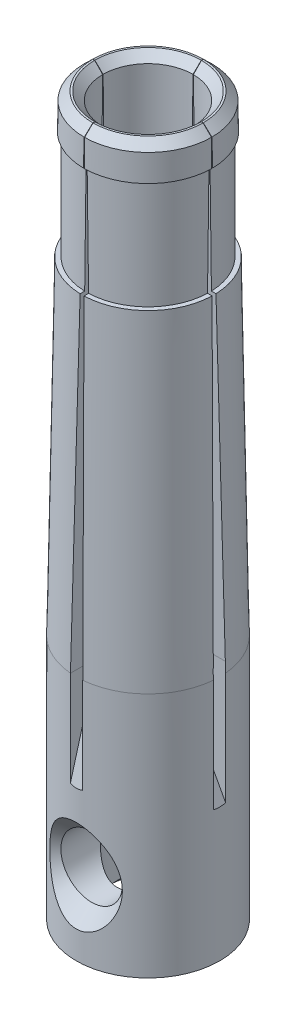
SolidWorks part; units mm, degrees
material "Brass"
ref_plane "Front Plane" through (0, 0, 0) normal (0, 0, 1) x (1, 0, 0)
ref_plane "Top Plane" through (0, 0, 0) normal (0, 1, 0) x (1, 0, 0)
ref_plane "Right Plane" through (0, 0, 0) normal (1, 0, 0) x (0, 0, -1)
sketch "Sketch1" plane through (0, 0, 0) normal (0, 0, 1) x (1, 0, 0)
  line L1 (0, 0) -> (3.5, 0)
  line L2 (0, 0) -> (0, 12)
  line L3 (0, 12) -> (3.5, 12)
  line L4 (3.5, 0) -> (3.5, 12)
  line L5 (0, 12) -> (3.5, 12)
  line L6 (0, 12) -> (0, 35)
  line L7 (0, 35) -> (3.1, 35)
  line L8 (3.5, 12) -> (3.1, 35)
  dimension "D1" = 3.5
  dimension "D2" = 12
  dimension "D3" = 3.1
  dimension "D4" = 35
revolve "Revolve1" add sketch "Sketch1" angle 360 about L2 region at (1.75, 6, 0) region at (1.652, 23.2677, 0)
sketch "Sketch2" plane through (0, 35, 0) normal (0, 1, 0) x (1, 0, 0)
  circle A0 centre (0, 0) radius 2.2
  dimension "D1" = 4.4
extrude "Cut-Extrude1" cut sketch "Sketch2" against normal blind 23
sketch "Sketch3" plane through (0, 0, 0) normal (0, -1, 0) x (1, 0, 0)
  line L0 (0, 0) -> (0, 50000) construction
  circle A0 centre (0, -0.5026) radius 2
  dimension "D1" = 4
extrude "Cut-Extrude2" cut sketch "Sketch3" against normal blind 9
ref_plane "Plane1" through (-3.5, 0, 0) normal (-1, 0, 0) x (0, 0, 1)
ref_plane "Plane2" through (0, 0, 3.5) normal (0, 0, 1) x (1, 0, 0)
sketch "Sketch5" plane through (-3.5, 0, 0) normal (-1, 0, 0) x (0, 0, 1)
  line L0 (0, 0) -> (0, 50000) construction
  line L1 (3.5, 12) -> (-3.5, 12) construction
  line L2 (3.5, 12) -> (-3.5, 12) construction
  line L3 (2.2, 35) -> (-2.2, 35) construction
  line L4 (3.1, 35) -> (-3.1, 35) construction
  line L5 (-3.5, 0) -> (3.5, 0) construction
  line L6 (0.3, 12) -> (-0.3, 12)
  line L7 (0.3, 12) -> (0.005, 35)
  line L8 (0.005, 35) -> (-0.005, 35)
  line L9 (-0.3, 12) -> (-0.005, 35)
  point P7 (0, 12)
  point P12 (0, 35)
  dimension "D1" = 12
  dimension "D2" = 0.6
  dimension "D3" = 0.01
extrude "Cut-Extrude3" cut sketch "Sketch5" against normal through all
sketch "Sketch9" plane through (0, 0, 3.5) normal (0, 0, 1) x (1, 0, 0)
  line L0 (3.1, 35) -> (-3.1, 35) construction
  line L1 (-3.5, 0) -> (3.5, 0) construction
  line L2 (-3.5, 9.5) -> (3.51, 9.5) construction
  line L3 (3.1, 35) -> (-3.1, 35) construction
  line L4 (0.005, 9.5) -> (0.005, 50009.5) construction
  line L8 (0.305, 12) -> (-0.295, 12)
  line L9 (0.305, 12) -> (0.01, 35)
  line L10 (0.01, 35) -> (0, 35)
  line L11 (-0.295, 12) -> (0, 35)
  point P6 (0.005, 9.5)
  point P7 (0.005, 35)
  point P13 (0.005, 12)
  dimension "D3" = 0.6
  dimension "D4" = 0.01
  dimension "D1" = 12
extrude "Cut-Extrude4" cut sketch "Sketch9" against normal through all
sketch "Sketch11" plane through (0, 0, 0) normal (0, 0, 1) x (1, 0, 0)
  line L0 (-3.5007, 0) -> (-3.5007, 11.8403) construction
  line L1 (-3.5007, 11.8403) -> (-3.4891, 11.8403) construction
  line L2 (-3.4891, 11.8403) -> (-3.1061, 34.8404) construction
  line L3 (-3.1061, 34.8404) -> (-0.0061, 31.7412) construction
  line L4 (-0.0061, 31.7412) -> (-0.2039, 16.1) construction
  line L5 (-0.2495, 12.5) -> (-3.598, 12.5) construction
  line L6 (-0.2039, 16.1) -> (0.305, 16.1) construction
  line L7 (0.305, 16.1) -> (0.397, 31.8919) construction
  line L9 (0.397, 31.8919) -> (3.4866, 31.8399) construction
  line L15 (3.4866, 31.8399) -> (3.4866, 8.8366) construction
  line L16 (3.4866, 8.8366) -> (3.5, 8.8364) construction
  line L17 (3.5, 8.8364) -> (3.4992, 0) construction
  line L18 (3.4992, 0) -> (-3.5007, 0) construction
  line L19 (-0.2495, 12.5) -> (-3.598, 12.5)
  line L20 (-3.598, 12.5) -> (-3.5007, 6.5)
  line L21 (-3.5007, 6.5) -> (-0.2495, 12.5)
  line L22 (-3.5, 0) -> (3.5, 0) construction
  line L23 (-3.4871, 12) -> (-2.1794, 12) construction
  line L24 (0, -3.85) -> (0, 3.85) construction
  line L25 (3.598, 12.5) -> (3.5007, 6.5)
  line L26 (0.2495, 12.5) -> (3.598, 12.5)
  line L27 (3.5007, 6.5) -> (0.2495, 12.5)
  dimension "D2" = 6.5
  dimension "D1" = 3.6
  dimension "D3" = 12.5
extrude "Cut-Extrude5" cut sketch "Sketch11" against normal blind 0.3 and the other way blind 0.3
sketch "Sketch22" plane through (0, 0, 0) normal (1, 0, 0) x (0, 0, -1)
  line L5 (-3.5, 12) -> (-3.5, 0)
  line L10 (1.9172, 5.7585) -> (1.9306, 5.7583) construction
  line L16 (3.6184, 12) -> (3.5, 7.3)
  line L17 (2.2, 12) -> (3.6184, 12)
  line L18 (3.5, 7.3) -> (2.2, 12)
  line L19 (3.5, 0) -> (3.5, 12)
  line L20 (3.5, 0) -> (3.5, 12) construction
  line L21 (-3.5, 12) -> (-3.5, 0)
  line L22 (3.5, 12) -> (-3.5, 12)
  line L23 (3.5, 12) -> (-3.5, 12) construction
  line L24 (-2.2, 12) -> (-3.6184, 12)
  line L25 (0, 0) -> (0, 9.5147) construction
  line L26 (-3.5, 7.3) -> (-2.2, 12)
  line L27 (-3.6184, 12) -> (-3.5, 7.3)
  point P6 (0, 12)
  dimension "D1" = 2.2
  dimension "D2" = 7.3
extrude "Cut-Extrude8" cut sketch "Sketch22" against normal blind 0.3 and the other way blind 0.3 contours L18 L16 L17 | L21 L26 L24 region at (0, 10.4333, 3.0667) region at (0, 10.4333, -3.0667) region at (0, 10.4333, -3.5395)
ref_plane "Plane3" through (0, 28, 0) normal (0, 1, 0) x (1, 0, 0)
sketch "Sketch15" plane through (0, 28, 0) normal (0, 1, 0) x (1, 0, 0)
  line L2 (3.4871, -0.3) -> (3.4784, -0.3)
  line L3 (3.4871, -0.3) -> (3.4784, -0.3)
  line L4 (3.4784, -0.3) -> (3.4789, -0.2936)
  line L5 (3.4784, -0.3) -> (3.4789, -0.2936)
  circle A1 centre (0, 0) radius 3.5
  arc A2 (0.01, -3.1) -> (3.1, -0.005) centre (0, 0) ccw
  circle A5 centre (0, 0) radius 3
  arc A8 (0.01, -3.1) -> (3.1, -0.005) centre (0, 0) ccw
  arc A9 (0.305, -3.4867) -> (3.4871, -0.3) centre (0, 0) ccw
  arc A10 (0.305, -3.4867) -> (3.4871, -0.3) centre (0, 0) ccw
  spline S2 degree 3 poles (4002.9422, -42.7726) (-49.9599, -29.2257) (85.4584, -2.005) (-99.4489, 25.1475) (-3996.4461, 36.8147) knots -3.390272 -3.390272 -3.390272 -3.390272 0.016411 2.969512 2.969512 2.969512 2.969512 only from (3.4789, -0.2936) to (3.1, -0.005)
  spline S3 degree 3 poles (3.4789, -0.2936) (3.3894, -0.2234) (3.2643, -0.1272) (3.1353, -0.031) (3.1, -0.005) knots 0 0 0 0 0.016411 0.022505 0.022505 0.022505 0.022505
  spline S4 degree 3 poles (-39.1544, 3996.2827) (-26.6987, 98.5154) (2.4129, -84.2826) (31.591, 46.9095) (46.3675, -4002.9006) knots -3.133969 -3.133969 -3.133969 -3.133969 0.016125 3.683871 3.683871 3.683871 3.683871 only from (0.01, -3.1) to (0.305, -3.4867)
  spline S5 degree 3 poles (0.01, -3.1) (0.0789, -3.1932) (0.1773, -3.323) (0.2756, -3.4492) (0.305, -3.4867) knots 0 0 0 0 0.016125 0.023005 0.023005 0.023005 0.023005
  dimension "D2" = 6
  dimension "D1" = 0
extrude "Cut-Extrude7" cut sketch "Sketch15" along normal blind 5.3 contours A1 | A5
ref_plane "Plane4" through (0, 0, 3.5) normal (0, 0, 1) x (1, 0, 0)
sketch "Sketch23" plane through (0, 0, 3.5) normal (0, 0, 1) x (1, 0, 0)
  line L0 (0, 0) -> (0, 50000) construction
  line L1 (-3.5, 0) -> (3.5, 0) construction
  point P3 (0, 3.6)
  dimension "D1" = 3.6
hole_wizard "CSK for M3 Oval Head Machine Screw1" positions "Sketch23" profile "Sketch24" countersink size "M3" standard "ANSI Metric" end condition up to next
sketch "Sketch24" plane through (0, 3.6, 3.5) normal (1, 0, 0) x (0, -1, 0)
  line L0 (0, 0) -> (0, 2.0026)
  line L1 (0, 2.0026) -> (1.5, 2.0026)
  line L2 (1.5, 2.0026) -> (1.5, 0.75)
  line L3 (1.5, 0.75) -> (2.25, 0)
  line L5 (2.25, 0) -> (0, 0)
  line L6 (-1.5, 0.75) -> (-2.25, 0) construction
  line L11 (0, -6.35) -> (0, 107.95) construction
  dimension "Thru Hole Dia." = 3
  dimension "Thru Hole Depth" = 2.0026
  dimension "Near C'Sink Dia." = 4.5
  dimension "Near C'Sink Angle" = 90
cosmetic thread "Cosmetic Thread1" parameters "D2"=4
chamfer "Chamfer1" distance 0.4 angle 45 9 edges at (-2.1903, 35, 2.1938) (2.1938, 35, 2.1903) (2.1938, 35, -2.1903) (-2.1903, 35, -2.1938) (-1.5539, 35, 1.5574) (1.5574, 35, 1.5539) (1.5574, 35, -1.5539) (-1.5539, 35, -1.5574) (0, 0, -2.5026) first distance on face at (-1.8827, 34.15, 1.8838) first distance on face at (1.8851, 34.15, 1.884) first distance on face at (1.887, 34.15, -1.8821) first distance on face at (-1.8808, 34.15, -1.8857) first distance on face at (-1.635, 19.8248, 1.0094) first distance on face at (1.6378, 19.8245, 1.0081) first distance on face at (1.6378, 19.8245, -1.0081) first distance on face at (-1.635, 19.8248, -1.0094) first distance on face at (-1.4997, 3.5685, 0.8206)
